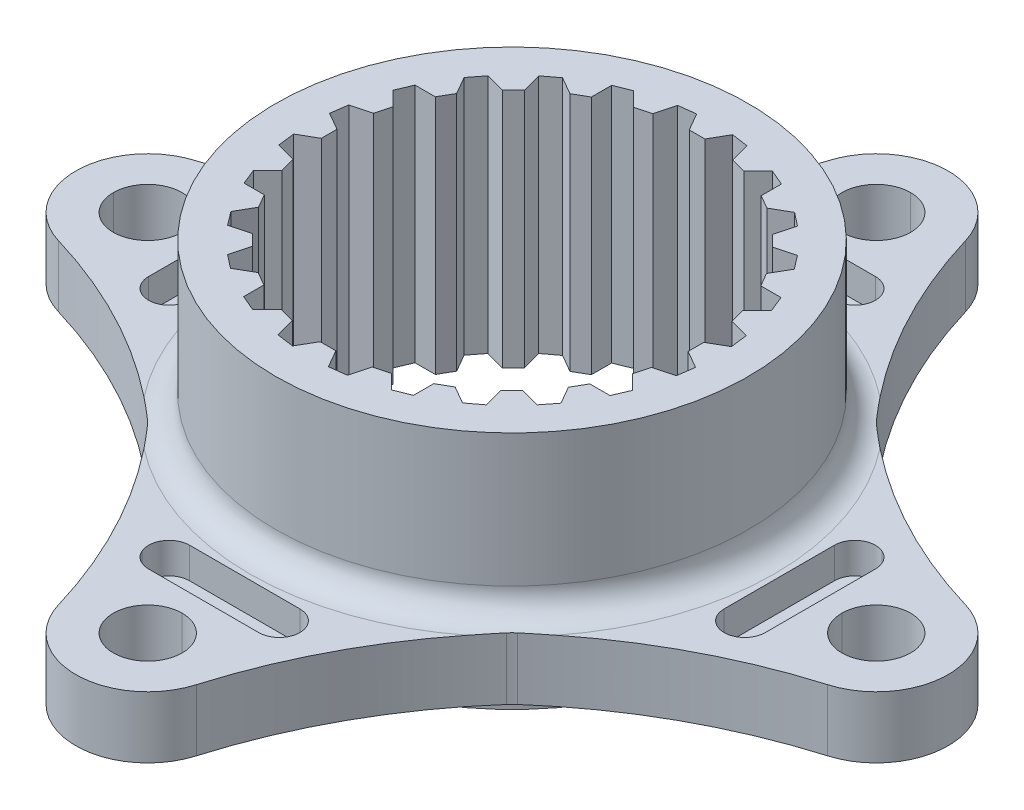
SolidWorks part; units mm, degrees
material "7075-T6 (SN)"
ref_plane "Front Plane" through (0, 0, 0) normal (0, 0, 1) x (1, 0, 0)
ref_plane "Top Plane" through (0, 0, 0) normal (0, 1, 0) x (1, 0, 0)
ref_plane "Right Plane" through (0, 0, 0) normal (1, 0, 0) x (0, 0, -1)
sketch "Sketch1" plane through (0, 0, 0) normal (0, 1, 0) x (1, 0, 0)
  line L0 (274.6284, 454.6081) -> (780.6456, 454.6081) construction
  circle A0 centre (0, 0) radius 23
  dimension "D1" = 46
sketch "Sketch5" plane through (0, 0, 0) normal (0, 1, 0) x (1, 0, 0)
  circle A0 centre (0, 0) radius 23
  circle A1 centre (0, 0) radius 25
  dimension "D1" = 46
  dimension "D2" = 50
sketch "Sketch6" plane through (0, 0, 0) normal (0, 1, 0) x (1, 0, 0)
  line L0 (-0.9689, -22.7363) -> (0.9689, -22.7363)
  line L1 (0.9689, -22.7363) -> (2.2189, -24.9013)
  line L2 (0, 33.3652) -> (0, -36.4848) construction
  line L3 (-0.9689, -22.7363) -> (-2.2189, -24.9013)
  line L4 (-4.9456, -22.1943) -> (-4.2985, -24.6091)
  line L5 (-6.8174, -21.6927) -> (-4.9456, -22.1943)
  line L6 (-6.8174, -21.6927) -> (-8.5852, -23.4605)
  line L7 (-10.5182, -22.6399) -> (-8.5852, -23.4605)
  line L8 (-10.5182, -20.1399) -> (-10.5182, -22.6399)
  line L9 (-12.1965, -19.171) -> (-10.5182, -20.1399)
  line L10 (-12.1965, -19.171) -> (-14.3615, -20.421)
  line L11 (-16.0164, -19.1281) -> (-14.3615, -20.421)
  line L12 (-15.3693, -16.7133) -> (-16.0164, -19.1281)
  line L13 (-16.7396, -15.343) -> (-15.3693, -16.7133)
  line L14 (-16.7396, -15.343) -> (-19.1544, -15.99)
  line L15 (-20.4182, -14.3129) -> (-19.1544, -15.99)
  line L16 (-19.1682, -12.1478) -> (-20.4182, -14.3129)
  line L17 (-20.1372, -10.4696) -> (-19.1682, -12.1478)
  line L18 (-20.1372, -10.4696) -> (-22.6372, -10.4696)
  line L19 (-23.4239, -8.5225) -> (-22.6372, -10.4696)
  line L20 (-21.6561, -6.7547) -> (-23.4239, -8.5225)
  line L21 (-22.1576, -4.8829) -> (-21.6561, -6.7547)
  line L22 (-22.1576, -4.8829) -> (-24.5725, -4.2358)
  line L23 (-24.8284, -2.1515) -> (-24.5725, -4.2358)
  line L24 (-22.6633, -0.9015) -> (-24.8284, -2.1515)
  line L25 (-22.6633, 1.0364) -> (-22.6633, -0.9015)
  line L26 (-22.6633, 1.0364) -> (-24.8284, 2.2864)
  line L27 (-24.5361, 4.366) -> (-24.8284, 2.2864)
  line L28 (-22.1213, 5.013) -> (-24.5361, 4.366)
  line L29 (-21.6197, 6.8849) -> (-22.1213, 5.013)
  line L30 (-21.6197, 6.8849) -> (-23.3875, 8.6526)
  line L31 (-22.567, 10.5857) -> (-23.3875, 8.6526)
  line L32 (-20.067, 10.5857) -> (-22.567, 10.5857)
  line L33 (-19.098, 12.2639) -> (-20.067, 10.5857)
  line L34 (-19.098, 12.2639) -> (-20.348, 14.429)
  line L35 (-19.0552, 16.0838) -> (-20.348, 14.429)
  line L36 (-16.6403, 15.4368) -> (-19.0552, 16.0838)
  line L37 (-15.27, 16.8071) -> (-16.6403, 15.4368)
  line L38 (-15.27, 16.8071) -> (-15.9171, 19.2219)
  line L39 (-14.24, 20.4857) -> (-15.9171, 19.2219)
  line L40 (-12.0749, 19.2357) -> (-14.24, 20.4857)
  line L41 (-10.3966, 20.2046) -> (-12.0749, 19.2357)
  line L42 (-10.3966, 20.2046) -> (-10.3966, 22.7046)
  line L43 (-8.4496, 23.4913) -> (-10.3966, 22.7046)
  line L44 (-6.6818, 21.7235) -> (-8.4496, 23.4913)
  line L45 (-4.8099, 22.2251) -> (-6.6818, 21.7235)
  line L46 (-4.8099, 22.2251) -> (-4.1629, 24.6399)
  line L47 (-2.0785, 24.8958) -> (-4.1629, 24.6399)
  line L48 (-0.8285, 22.7308) -> (-2.0785, 24.8958)
  line L49 (1.1093, 22.7308) -> (-0.8285, 22.7308)
  line L50 (1.1093, 22.7308) -> (2.3593, 24.8958)
  line L51 (4.4389, 24.6036) -> (2.3593, 24.8958)
  line L52 (5.086, 22.1888) -> (4.4389, 24.6036)
  line L53 (6.9578, 21.6872) -> (5.086, 22.1888)
  line L54 (6.9578, 21.6872) -> (8.7256, 23.455)
  line L55 (10.6586, 22.6344) -> (8.7256, 23.455)
  line L56 (10.6586, 20.1344) -> (10.6586, 22.6344)
  line L57 (12.3369, 19.1655) -> (10.6586, 20.1344)
  line L58 (12.3369, 19.1655) -> (14.5019, 20.4155)
  line L59 (16.1568, 19.1226) -> (14.5019, 20.4155)
  line L60 (15.5097, 16.7078) -> (16.1568, 19.1226)
  line L61 (16.88, 15.3375) -> (15.5097, 16.7078)
  line L62 (16.88, 15.3375) -> (19.2948, 15.9845)
  line L63 (20.5586, 14.3074) -> (19.2948, 15.9845)
  line L64 (19.3086, 12.1424) -> (20.5586, 14.3074)
  line L65 (20.2776, 10.4641) -> (19.3086, 12.1424)
  line L66 (20.2776, 10.4641) -> (22.7776, 10.4641)
  line L67 (23.5643, 8.517) -> (22.7776, 10.4641)
  line L68 (21.7965, 6.7492) -> (23.5643, 8.517)
  line L69 (22.298, 4.8774) -> (21.7965, 6.7492)
  line L70 (22.298, 4.8774) -> (24.7129, 4.2303)
  line L71 (24.9688, 2.146) -> (24.7129, 4.2303)
  line L72 (22.8037, 0.896) -> (24.9688, 2.146)
  line L73 (22.8037, -1.0419) -> (22.8037, 0.896)
  line L74 (22.8037, -1.0419) -> (24.9688, -2.2919)
  line L75 (24.6765, -4.3714) -> (24.9688, -2.2919)
  line L76 (22.2617, -5.0185) -> (24.6765, -4.3714)
  line L77 (21.7601, -6.8903) -> (22.2617, -5.0185)
  line L78 (21.7601, -6.8903) -> (23.5279, -8.6581)
  line L79 (22.7074, -10.5912) -> (23.5279, -8.6581)
  line L80 (20.2074, -10.5912) -> (22.7074, -10.5912)
  line L81 (19.2384, -12.2694) -> (20.2074, -10.5912)
  line L82 (19.2384, -12.2694) -> (20.4884, -14.4345)
  line L83 (19.1955, -16.0893) -> (20.4884, -14.4345)
  line L84 (16.7807, -15.4423) -> (19.1955, -16.0893)
  line L85 (15.4104, -16.8126) -> (16.7807, -15.4423)
  line L86 (15.4104, -16.8126) -> (16.0575, -19.2274)
  line L87 (14.3804, -20.4912) -> (16.0575, -19.2274)
  line L88 (12.2153, -19.2412) -> (14.3804, -20.4912)
  line L89 (10.537, -20.2101) -> (12.2153, -19.2412)
  line L90 (10.537, -20.2101) -> (10.537, -22.7101)
  line L91 (8.59, -23.4968) -> (10.537, -22.7101)
  line L92 (6.8222, -21.729) -> (8.59, -23.4968)
  line L93 (4.9503, -22.2306) -> (6.8222, -21.729)
  line L94 (4.9503, -22.2306) -> (4.3033, -24.6454)
  line L95 (2.2189, -24.9013) -> (4.3033, -24.6454)
  line L96 (-4.2985, -24.6091) -> (-2.2189, -24.9013)
  circle A0 centre (0, 0) radius 23 construction
  circle A1 centre (0, 0) radius 25 construction
  point P11 (0, -23)
  point P131 (0.0702, -0.0027)
  dimension "D4" = 2.5
  dimension "D1" = 2.1
  dimension "D5" = 112
  dimension "D6" = 120
  dimension "D2" = 1.9379
  dimension "D3" = 24
sketch "Sketch8" plane through (0, 0, 0) normal (0, 1, 0) x (1, 0, 0)
  circle A0 centre (0, 0) radius 100
  dimension "D1" = 200
extrude "Boss-Extrude4" add sketch "Sketch8" along normal blind 27.178 contours A0
extrude "Cut-Extrude1" cut sketch "Sketch6" along normal through all
sketch "Sketch9" plane through (0, 27.178, 0) normal (0, 1, 0) x (1, 0, 0)
  circle A0 centre (0, 0) radius 29.21
  dimension "D1" = 58.42
extrude "Cut-Extrude3" cut sketch "Sketch9" against normal blind 19.558 flip side to cut
sketch "Sketch10" plane through (0, 7.62, 0) normal (0, 1, 0) x (1, 0, 0)
  circle A1 centre (0, 45.0088) radius 4.2545
  circle A4 centre (45.0088, 0) radius 4.2545
  circle A5 centre (0, -45.0088) radius 4.2545
  circle A6 centre (-45.0088, 0) radius 4.2545
  point P11 (0, 0)
  point P28 (0, 0)
  dimension "D1" = 4
  dimension "D2" = 8.509
  dimension "D3" = 45.0088
sketch "Sketch11" plane through (0, 7.62, 0) normal (0, 1, 0) x (1, 0, 0)
  line L0 (0, 45.0088) -> (45.0088, 0) construction
  line L1 (0, 0) -> (70.7107, 70.7107) construction
  line L2 (0, 45.0088) -> (8.89, 45.0088) construction
  line L3 (0, 45.0088) -> (8.5239, 47.5337) construction
  circle A0 centre (0, 0) radius 100 construction
  arc A1 (8.5239, 47.5337) -> (22.5044, 22.5044) centre (71.1084, 66.0721) ccw
  arc A2 (47.5337, 8.5239) -> (22.5044, 22.5044) centre (66.0721, 71.1084) cw
  arc A3 (47.5337, -8.5239) -> (22.5044, -22.5044) centre (66.0721, -71.1084) ccw
  arc A4 (-8.5239, -47.5337) -> (-22.5044, -22.5044) centre (-71.1084, -66.0721) ccw
  arc A5 (-47.5337, 8.5239) -> (-22.5044, 22.5044) centre (-66.0721, 71.1084) ccw
  arc A6 (8.5239, -47.5337) -> (22.5044, -22.5044) centre (71.1084, -66.0721) cw
  arc A7 (-47.5337, -8.5239) -> (-22.5044, -22.5044) centre (-66.0721, -71.1084) cw
  circle A8 centre (0, 45.0088) radius 8.89
  circle A9 centre (45.0088, 0) radius 8.89
  circle A10 centre (0, -45.0088) radius 8.89
  circle A11 centre (-45.0088, 0) radius 8.89
  arc A12 (-8.5239, 47.5337) -> (-22.5044, 22.5044) centre (-71.1084, 66.0721) cw
  point P15 (0, 0)
  point P31 (0, 0)
  point P37 (0, 0)
  point P42 (0, 0)
  point P51 (0, 0)
  circle M10 centre (0, 0) radius 100
  dimension "D4" = 4
  dimension "D1" = 4
  dimension "D2" = 17.78
  dimension "D5" = 4
  dimension "D3" = 16.5
extrude "Cut-Extrude6" cut sketch "Sketch11" against normal blind 7.62 contours A11 A8 A9 A10 M10 region at (-97.1716, 7.62, 0)
extrude "Cut-Extrude7" cut sketch "Sketch10" against normal blind 7.62
fillet "Fillet2" radius 3.175 1 edges at (0, 7.62, 29.21)
ref_plane "Plane1" through (0, 0, 0) normal (0, 0, 1) x (1, 0, 0)
ref_plane "Plane2" through (0, 0, 0) normal (-1, 0, 0) x (0, 0, 1)
split line "Split Line1"
split line "Split Line2"
ref_axis "Axis1" through (0, 8.001, 0) along (0, -1, 0)
fillet "Fillet3" radius 7.62 4 edges at (-22.5044, 3.8348, -22.5044) (22.5044, 3.8348, -22.5044) (22.5044, 3.8348, 22.5044) (-22.5044, 3.8348, 22.5044)
sketch "Sketch13" plane through (0, 7.62, 0) normal (0, 1, 0) x (1, 0, 0)
  line L0 (0, 4.191) -> (0, -4.191) construction
  line L1 (-8.4262, 38.1) -> (8.4262, 38.1)
  line L2 (-8.4262, 38.1) -> (-10.795, 33.02)
  line L3 (-10.795, 33.02) -> (10.795, 33.02)
  line L4 (8.4262, 38.1) -> (10.795, 33.02)
  point P11 (0, 33.02)
  dimension "D1" = 115
  dimension "D2" = 115
  dimension "D3" = 5.08
  dimension "D4" = 0
  dimension "D5" = 21.59
  dimension "D6" = 33.02
extrude "Cut-Extrude12" cut sketch "Sketch13" against normal blind 3.81 contours L1 L4 L3 L2
fillet "Fillet5" radius 2.54 4 edges at (-10.795, 5.715, -33.02) (10.795, 5.715, -33.02) (-8.4262, 5.715, -38.1) (8.4262, 5.715, -38.1)
pattern_circular "CirPattern1" count 4 over 360 about axis through (0, 8.001, 0) along (0, -1, 0) of "Cut-Extrude12", "Fillet5"
sketch "Sketch14" plane through (0, 0, 0) normal (0, -1, 0) x (1, 0, 0)
  circle A0 centre (0, 0) radius 29.0322
  dimension "D1" = 58.0644
extrude "Boss-Extrude5" add sketch "Sketch14" along normal blind 2.54
extrude "Cut-Extrude17" cut sketch "Sketch6<5>" against normal blind 2.54
sketch "Sketch6<5>" plane through (0, 0, 0) normal (0, 1, 0) x (1, 0, 0) same geometry as "Sketch6"
